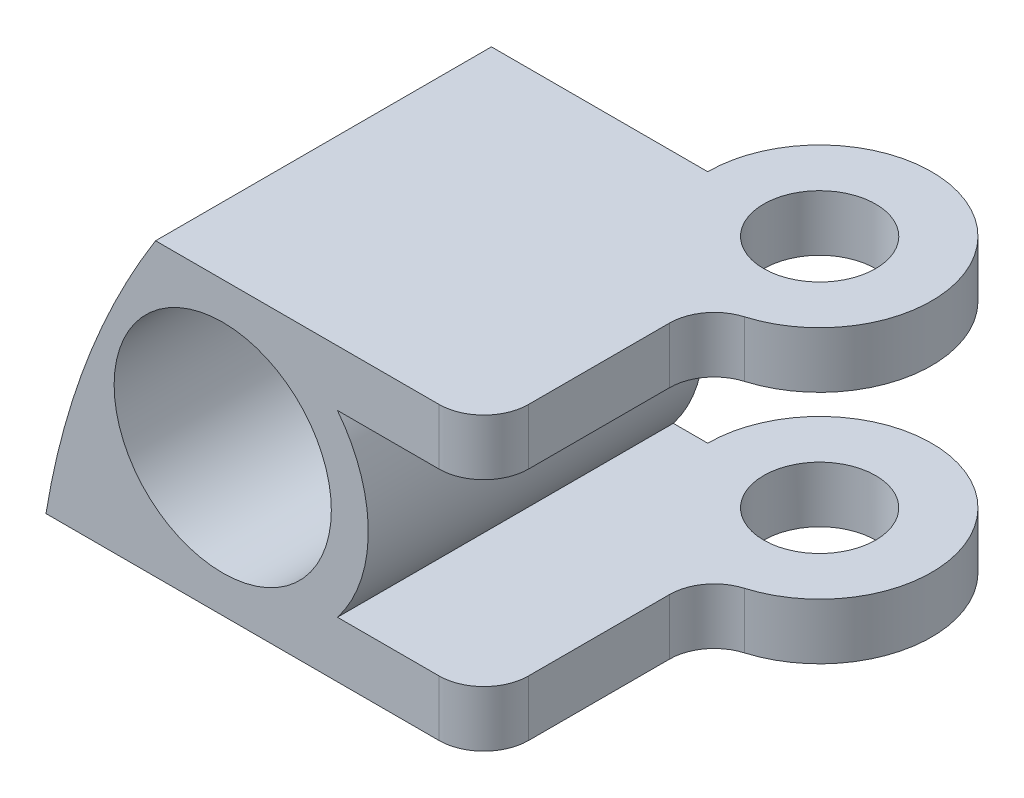
SolidWorks part; units mm, degrees
ref_plane "Front Plane" through (0, 0, 0) normal (0, 0, 1) x (1, 0, 0)
ref_plane "Top Plane" through (0, 0, 0) normal (0, 1, 0) x (1, 0, 0)
ref_plane "Right Plane" through (0, 0, 0) normal (1, 0, 0) x (0, 0, -1)
sketch "Sketch1" plane through (0, 0, 0) normal (0, 0, 1) x (1, 0, 0)
  line L0 (0, 47.6885) -> (0, -47.6885) construction
  line L1 (-22.225, 31.1085) -> (-15.875, 31.1085) construction
  line L2 (-22.225, 31.1085) -> (-22.225, -16.5165) construction
  line L3 (-22.225, -16.5165) -> (-15.875, -16.5165) construction
  line L4 (-15.875, 31.1085) -> (-15.875, -16.5165) construction
  line L5 (15.875, -24.8854) -> (22.225, -24.8854) construction
  line L6 (15.875, -24.8854) -> (15.875, 31.1085) construction
  line L7 (15.875, 31.1085) -> (22.225, 31.1085) construction
  line L8 (22.225, -24.8854) -> (22.225, 31.1085) construction
  line L10 (-31.75, 31.1085) -> (31.75, 31.1085) construction
  line L11 (-31.75, 31.1085) -> (-31.75, 26.346) construction
  line L12 (-31.75, 26.346) -> (31.75, 26.346) construction
  line L13 (31.75, 31.1085) -> (31.75, 26.346) construction
  line L14 (-31.75, -16.5165) -> (31.75, -16.5165) construction
  line L15 (-31.75, -16.5165) -> (-31.75, -11.754) construction
  line L16 (-31.75, -11.754) -> (31.75, -11.754) construction
  line L17 (31.75, -16.5165) -> (31.75, -11.754) construction
  line L18 (31.75, -24.8854) -> (-31.75, -24.8854) construction
  line L19 (31.75, -24.8854) -> (31.75, -20.1229) construction
  line L20 (31.75, -20.1229) -> (-31.75, -20.1229) construction
  line L21 (-31.75, -24.8854) -> (-31.75, -20.1229) construction
  line L22 (-22.225, 31.1085) -> (-15.875, 31.1085) construction
  line L23 (-22.225, 31.1085) -> (-22.225, 32.696) construction
  line L24 (-22.225, 32.696) -> (-15.875, 32.696) construction
  line L25 (-15.875, 31.1085) -> (-15.875, 32.696) construction
  line L26 (15.875, 31.1085) -> (22.225, 31.1085) construction
  line L27 (15.875, 31.1085) -> (15.875, 32.696) construction
  line L28 (15.875, 32.696) -> (22.225, 32.696) construction
  line L29 (22.225, 31.1085) -> (22.225, 32.696) construction
  circle A0 centre (0, 0) radius 47.6885 construction
  circle A3 centre (-12.7, -31.2354) radius 6.35 construction
  circle A4 centre (-12.7, -31.2354) radius 12.7 construction
  circle A5 centre (-12.7, -31.2354) radius 13.97 construction
  circle A6 centre (12.7, -31.2354) radius 6.35 construction
  circle A7 centre (12.7, -31.2354) radius 13.97 construction
  circle A8 centre (12.7, -31.2354) radius 12.7 construction
  circle A9 centre (-31.7965, 14.7814) radius 8.255
  circle A10 centre (-31.7965, -1.7286) radius 8.255
  circle A11 centre (0, 0) radius 44.45
  point P44 (0, 0)
  point P45 (19.05, 32.696)
  point P46 (-19.05, 32.696)
  point P47 (0, 0)
  dimension "D1" = 95.377
  dimension "D6" = 12.7
  dimension "D7" = 25.4
  dimension "D8" = 27.94
  dimension "D9" = 16.51
  dimension "D10" = 16.51
  dimension "D13" = 88.9
  dimension "D2" = 47.625
  dimension "D3" = 6.35
  dimension "D4" = 6.35
  dimension "D5" = 19.05
  dimension "D11" = 63.5
  dimension "D12" = 4.7625
  dimension "D14" = 1.5875
  dimension "D15" = 1.5875
  dimension "D16" = 63.5
  dimension "D17" = 63.5
  dimension "D18" = 31.75
  dimension "D19" = 19.05
sketch "Sketch2" plane through (0, 0, 0) normal (0, 0, 1) x (1, 0, 0)
  line L2 (-37.667, 23.6008) -> (-13.4018, 23.6008)
  line L5 (-27.3506, 10.2658) -> (-13.4018, 10.2658)
  line L6 (-13.4018, 7.0908) -> (-13.4018, 10.2658)
  line L7 (-27.3506, 20.4258) -> (-13.4018, 20.4258)
  line L10 (-13.4018, 20.4258) -> (-13.4018, 23.6008)
  line L11 (-43.8808, 7.0908) -> (-13.4018, 7.0908)
  line L12 (0, 44.45) -> (0, -44.45) construction
  circle A0 centre (-33.8574, 15.3458) radius 6.1595
  arc A1 (-27.3506, 10.2658) -> (-27.3506, 20.4258) centre (-33.8574, 15.3458) ccw
  circle A2 centre (0, 0) radius 44.45 construction
  arc A3 (-43.8808, 7.0908) -> (-37.667, 23.6008) centre (0, 0) cw
  point P11 (-33.8574, 15.3458)
  dimension "D1" = 12.319
  dimension "D2" = 16.51
  dimension "D3" = 88.9
  dimension "D4" = 10.16
  dimension "D5" = 3.175
extrude "Boss-Extrude1" add sketch "Sketch2" along normal blind 25.4
sketch "Sketch3" plane through (0, 23.6008, 0) normal (0, 1, 0) x (1, 0, 0)
  line L0 (-25.4, 0) -> (0, 0) construction
  line L2 (-22.225, 0) -> (-22.225, -25.4) construction
  line L3 (-13.4018, 0) -> (-37.667, 0) construction
  line L4 (-13.4018, -25.4) -> (-37.667, -25.4) construction
  circle A0 centre (-19.05, -6.35) radius 3.175
  point P4 (0, 0)
  dimension "D1" = 6.35
  dimension "D2" = 6.35
  dimension "D3" = 3.175
extrude "Cut-Extrude1" cut sketch "Sketch3" against normal blind 25.4
sketch "Sketch6" plane through (0, 23.6008, 0) normal (0, 1, 0) x (1, 0, 0)
  line L2 (-40.64, 0) -> (-46.99, 0)
  line L3 (-40.64, -6.35) -> (-25.4, -6.35)
  line L9 (-19.05, -12.7) -> (-19.05, -25.4)
  line L10 (-13.4018, -25.4) -> (-37.667, -25.4) construction
  line L11 (-19.05, -25.4) -> (-13.4018, -25.4)
  line L12 (-40.64, 0) -> (-25.4, 3.0881)
  line L13 (-25.4, 3.0881) -> (-9.028, 2.4683)
  line L14 (-9.028, 2.4683) -> (-10.3297, -21.0851)
  line L15 (-10.3297, -21.0851) -> (-13.4018, -25.4)
  arc A0 (-46.99, 0) -> (-40.64, -6.35) centre (-46.99, -6.35) ccw
  arc A2 (-19.05, -12.7) -> (-25.4, -6.35) centre (-19.05, -6.35) ccw
  dimension "D1" = 12.7
  dimension "D2" = 27.94
  dimension "D3" = 12.7
extrude "Cut-Extrude2" cut sketch "Sketch6" against normal through all
sketch "Sketch7" plane through (0, 23.6008, 0) normal (0, 1, 0) x (1, 0, 0)
  circle A0 centre (-19.05, -6.35) radius 6.35
  circle A1 centre (-19.05, -6.35) radius 3.175
extrude "Boss-Extrude2" add sketch "Sketch7" against normal up to surface (3.175 mm away) up to face at (-19.05, 20.4258, 9.525)
sketch "Sketch8" plane through (0, 7.0908, 0) normal (0, -1, 0) x (1, 0, 0)
  circle A0 centre (-19.05, 6.35) radius 3.175
  circle A1 centre (-19.05, 6.35) radius 6.35
extrude "Boss-Extrude3" add sketch "Sketch8" against normal up to surface (3.175 mm away) up to face at (-19.05, 10.2658, 3.175)
fillet "Fillet1" radius 2.54 2 edges at (-19.05, 22.0133, 12.7) (-19.05, 8.6783, 12.7)
fillet "Fillet2" radius 2.54 2 edges at (-19.05, 8.6783, 25.4) (-19.05, 22.0133, 25.4)
